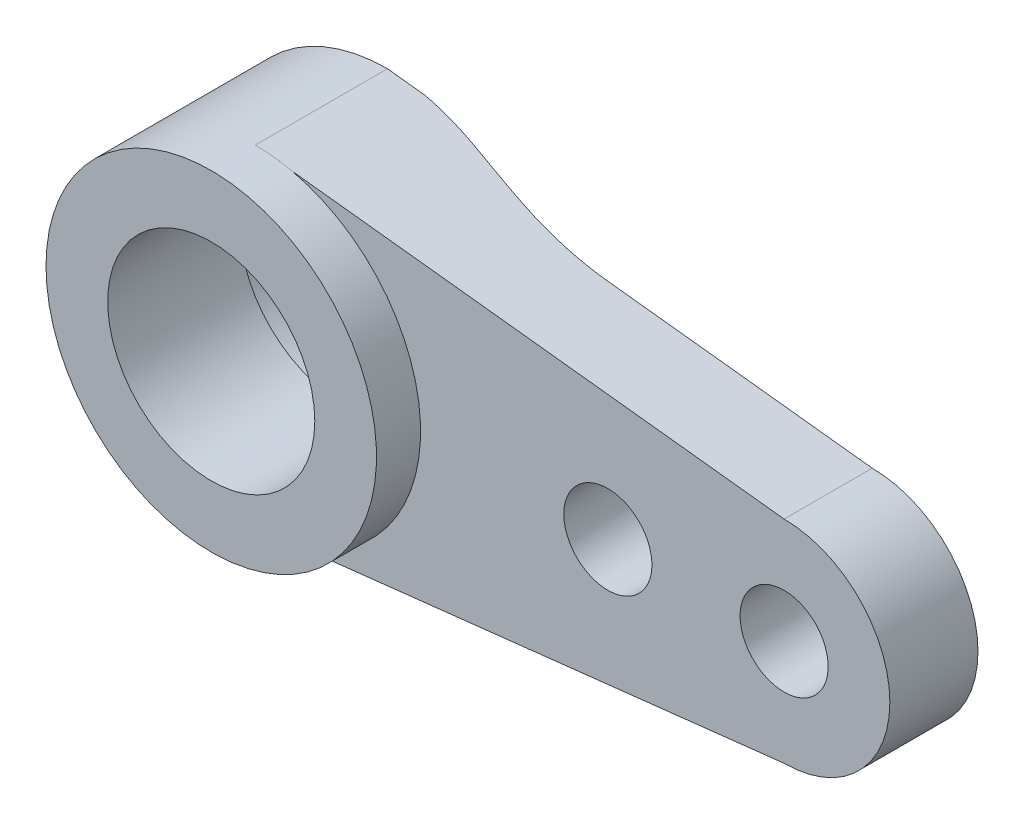
SolidWorks part; units mm, degrees
ref_plane "Front Plane" through (0, 0, 0) normal (0, 0, 1) x (1, 0, 0)
ref_plane "Top Plane" through (0, 0, 0) normal (0, 1, 0) x (1, 0, 0)
ref_plane "Right Plane" through (0, 0, 0) normal (1, 0, 0) x (0, 0, -1)
sketch "Sketch1" plane through (0, 0, 0) normal (0, 0, 1) x (1, 0, 0)
  line L0 (0, 3.75) -> (12, 2.4)
  line L1 (0, -3.75) -> (12, -2.4)
  arc A0 (0.8332, 3.6563) -> (0.8332, -3.6563) centre (0, 0) ccw
  arc A1 (12, -2.4) -> (12, 2.4) centre (12, 0) ccw
  circle A2 centre (0, 0) radius 2.35
  dimension "D1" = 7.5
  dimension "D2" = 4.8
  dimension "D4" = 4.7
  dimension "D3" = 12
extrude "Boss-Extrude1" add sketch "Sketch1" along normal blind 2 contours L1 A1 L0 A0 A2 region at (5.629, 0, 0)
sketch "Sketch2" plane through (0, 0, 2) normal (0, 0, 1) x (1, 0, 0)
  line L2 (0, -3.75) -> (12, -2.4)
  line L3 (12, 2.4) -> (0, 3.75)
  circle A0 centre (0, 0) radius 2.35 construction
  circle A1 centre (0, 0) radius 2.35
  arc A2 (12, -2.4) -> (12, 2.4) centre (12, 0) ccw
  arc A3 (0, 3.75) -> (0, -3.75) centre (0, 0) ccw
  arc A5 (0, 3.75) -> (0, -3.75) centre (0, 0) ccw
  arc A6 (0, 3.75) -> (0, -3.75) centre (0, 0) cw
  dimension "D1" = 0
extrude "Boss-Extrude2" add sketch "Sketch2" along normal blind 1
sketch "Sketch3" plane through (0, 0, 0) normal (0, 0, -1) x (-1, 0, 0)
  line L2 (-12, -2.4) -> (0, -3.75)
  line L3 (0, 3.75) -> (-12, 2.4)
  circle A0 centre (0, 0) radius 2.35 construction
  circle A1 centre (0, 0) radius 2.35
  arc A2 (0, -3.75) -> (0, 3.75) centre (0, 0) ccw
  arc A3 (-12, 2.4) -> (-12, -2.4) centre (-12, 0) ccw
  arc A4 (0, -3.75) -> (0, 3.75) centre (0, 0) ccw
  circle A6 centre (0, 0) radius 2.75
  arc A7 (0, 3.75) -> (0, -3.75) centre (0, 0) ccw
  line M6 (-12, -2.4) -> (0, -3.75)
  arc M7 (0, -3.75) -> (0, 3.75) centre (0, 0) ccw
  line M8 (0, 3.75) -> (-12, 2.4)
  dimension "D2" = 5.5
  dimension "D1" = 0
extrude "Boss-Extrude3" add sketch "Sketch3" along normal blind 1 contours A7 A6 M8 M6 M7 region at (3.6439, 0, 0)
fillet "Fillet1" radius 5 1 edges at (3.75, 0, 0)
sketch "Sketch4" plane through (0, 0, 0) normal (0, 0, -1) x (-1, 0, 0)
  line L0 (0, 0) -> (-8, 0) construction
  circle A3 centre (-12, 0) radius 1
  circle A4 centre (-8, 0) radius 1
  dimension "D1" = 2
  dimension "D2" = 2
  dimension "D3" = 8
  dimension "D4" = 12
extrude "Cut-Extrude1" cut sketch "Sketch4" against normal up to next
